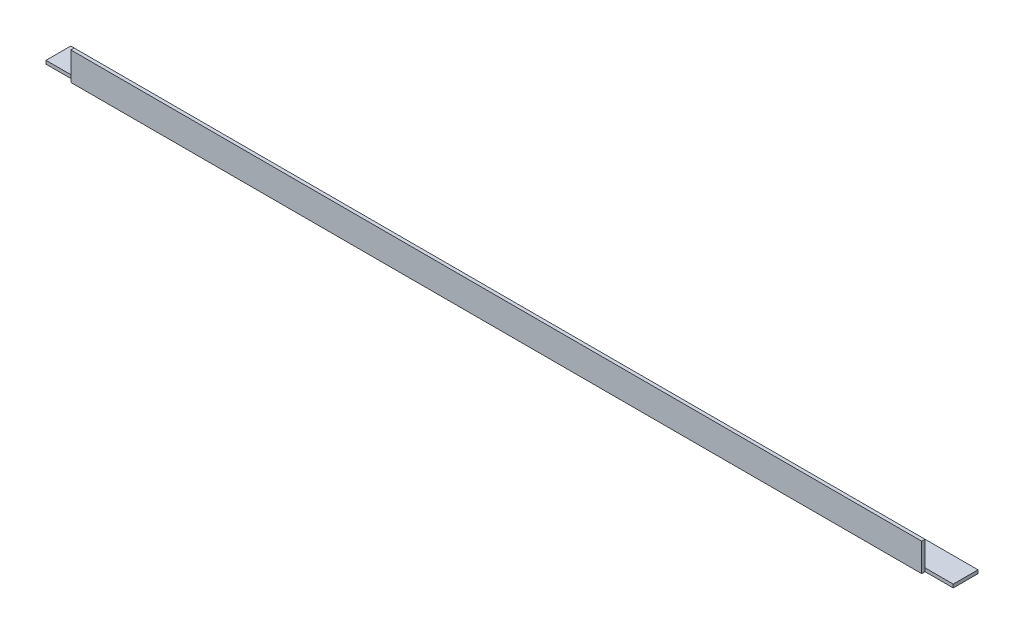
SolidWorks part; units mm, degrees
ref_plane "Спереди" through (0, 0, 0) normal (0, 0, 1) x (1, 0, 0)
ref_plane "Сверху" through (0, 0, 0) normal (0, 1, 0) x (1, 0, 0)
ref_plane "Справа" through (0, 0, 0) normal (1, 0, 0) x (0, 0, -1)
sketch "Эскиз1" plane through (0, 0, 0) normal (1, 0, 0) x (0, 0, -1)
  line L0 (0, 25) -> (0, 0)
  line L1 (0, 0) -> (25, 0)
extrude "Вытянуть-Тонкостенный1" add sketch "Эскиз1" along normal blind 806 thin thin type one direction reverse wall 3
sketch "Эскиз2" plane through (0, 0, 0) normal (0, -1, 0) x (1, 0, 0)
  line L1 (806, 0) -> (781, 0)
  line L2 (806, 0) -> (806, -3)
  line L3 (806, -3) -> (781, -3)
  line L4 (781, 0) -> (781, -3)
  line L5 (0, 0) -> (25, 0)
  line L6 (0, 0) -> (0, -3)
  line L7 (0, -3) -> (25, -3)
  line L8 (25, 0) -> (25, -3)
extrude "Вырез-Вытянуть1" cut sketch "Эскиз2" against normal through all
